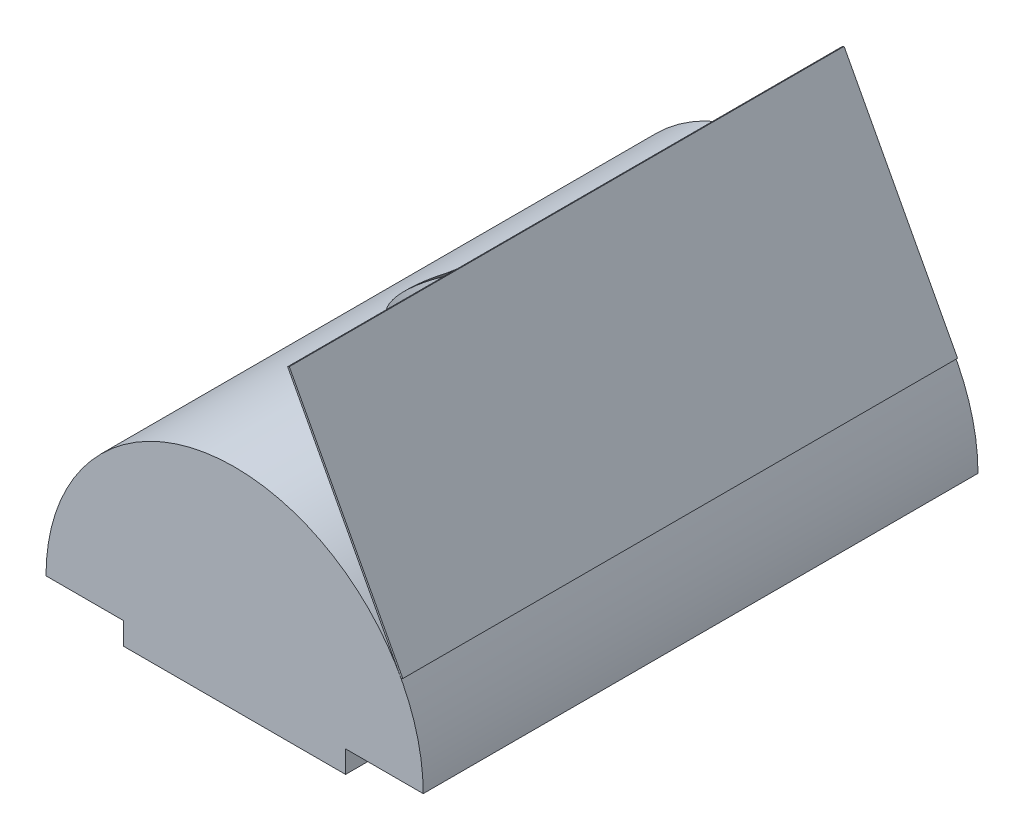
SolidWorks part; units mm, degrees
ref_plane "前视基准面" through (0, 0, 0) normal (0, 0, 1) x (1, 0, 0)
ref_plane "上视基准面" through (0, 0, 0) normal (0, 1, 0) x (1, 0, 0)
ref_plane "右视基准面" through (0, 0, 0) normal (1, 0, 0) x (0, 0, -1)
sketch "草图1" plane through (0, 0, 0) normal (0, 0, 1) x (1, 0, 0)
  line L0 (-6.8, 0) -> (-4, 0)
  line L1 (4, 0) -> (6.8, 0)
  line L2 (-4, 0) -> (-4, -0.8)
  line L3 (4, 0) -> (4, -0.8)
  line L4 (-4, -0.8) -> (4, -0.8)
  arc A0 (6.8, 0) -> (-6.8, 0) centre (0, 0) ccw
  dimension "D1" = 13.6
extrude "凸台-拉伸1" add sketch "草图1" along normal blind 20
sketch "草图2" plane through (0, -0.8, 0) normal (0, -1, 0) x (1, 0, 0)
  circle A0 centre (0, 10.3972) radius 3
  dimension "D1" = 6
extrude "切除-拉伸1" cut sketch "草图2" against normal blind 20
sketch "草图3" plane through (0, -0.8, 0) normal (0, -1, 0) x (1, 0, 0)
  circle A0 centre (0, 10.3972) radius 3 construction
  circle A1 centre (0, 10.3972) radius 3
curve "螺旋线/涡状线1" pitch 1 height 8 radius 3 centre (0, -0.8, 10.3972) axis (0, 1, 0) start towards (0.7071, 0, 0.7071)
sketch "草图4" plane through (0, 0, 0) normal (1, 0, 0) x (0, 0, -1)
  line L0 (-7.3972, -0.025) -> (-7.3972, -0.825)
  line L2 (-7.3972, -0.425) -> (-6.9972, -0.425) construction
  line L3 (-7.3972, -0.025) -> (-6.9972, -0.425)
  line L4 (-6.9972, -0.425) -> (-7.3972, -0.825)
  dimension "D1" = 0.8
  dimension "D2" = 0.4
sweep "切除-扫描1" cut profiles "草图4" path "螺旋线/涡状线1"
sketch "草图5" plane through (0, 0, 20) normal (0, 0, 1) x (1, 0, 0)
  line L0 (6.0037, 3.1931) -> (1.9118, 10.8865)
  line L1 (1.9118, 10.8865) -> (1.9712, 10.9181)
  line L2 (1.9712, 10.9181) -> (6.063, 3.2247)
  line L3 (6.063, 3.2247) -> (6.0037, 3.1931)
  arc A0 (6.8, 0) -> (-6.8, 0) centre (0, 0) ccw construction
extrude "凸台-拉伸2" add sketch "草图5" against normal blind 20 separate body
